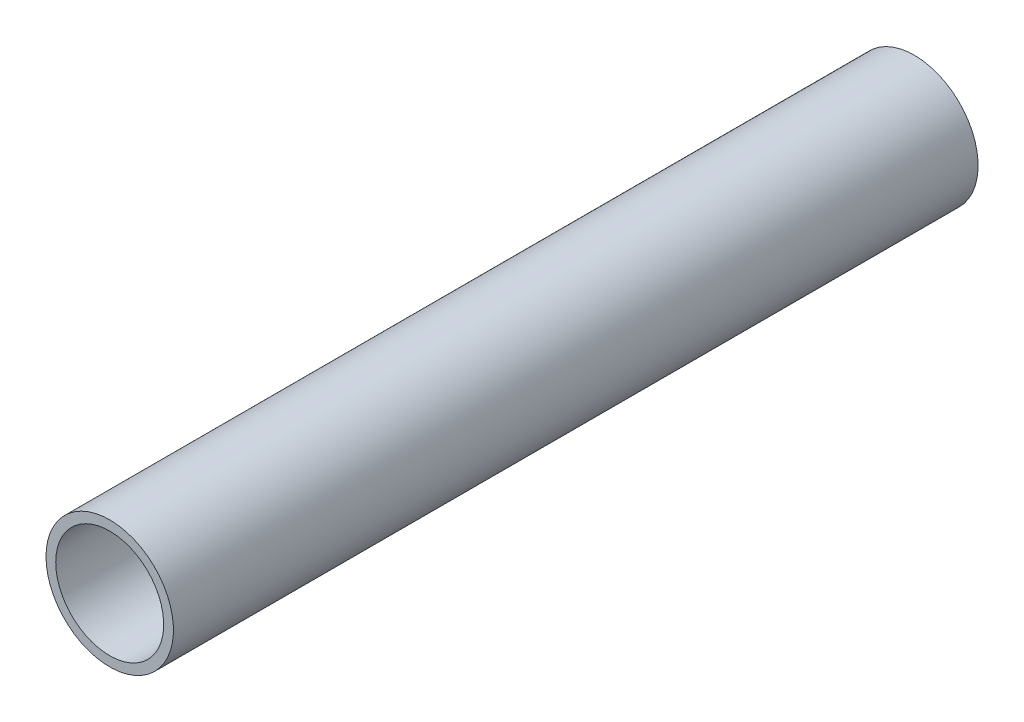
SolidWorks part; units mm, degrees
ref_plane "Front Plane" through (0, 0, 0) normal (1, 0, 0) x (0, 1, 0)
ref_plane "Top Plane" through (0, 0, 0) normal (0, 0, 1) x (0, 1, 0)
ref_plane "Right Plane" through (0, 0, 0) normal (0, 1, 0) x (-1, 0, 0)
sketch "Sketch2" plane through (0, 0, 0) normal (0, 0, 1) x (0, 1, 0)
  line L0 (0, 0) -> (24.13, 0) construction
  circle A0 centre (0, 0) radius 24.13
  circle A1 centre (0, 0) radius 20.447
  dimension "D1" = 40.894
  dimension "D2" = 48.26
extrude "base" add sketch "Sketch2" along normal blind 304.8
sketch "Sketch3" plane through (0, 0, 0) normal (0, 0, -1) x (1, 0, 0)
  circle A0 centre (0, 0) radius 21.9075
  circle A1 centre (0, 0) radius 20.447
  circle A2 centre (0, 0) radius 20.447 construction
  dimension "D1" = 43.815
extrude "snap_ring_groove" cut sketch "Sketch3" against normal blind 1.7272 from offset 6.35 offset against normal yes
